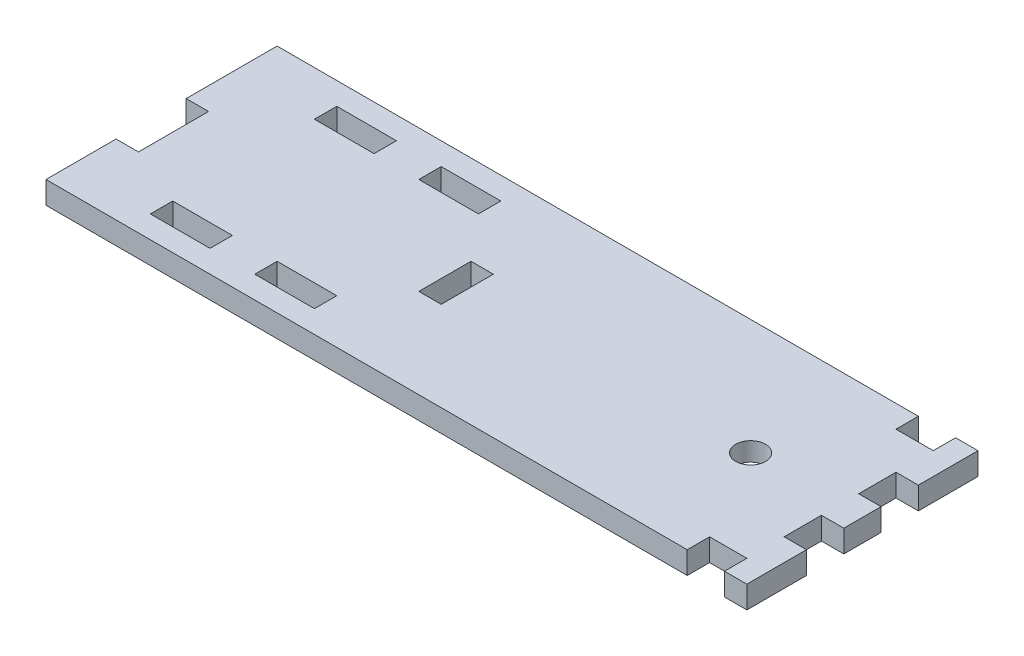
SolidWorks part; units mm, degrees
ref_plane "Front Plane" through (0, 0, 0) normal (0, 0, 1) x (1, 0, 0)
ref_plane "Top Plane" through (0, 0, 0) normal (0, 1, 0) x (1, 0, 0)
ref_plane "Right Plane" through (0, 0, 0) normal (1, 0, 0) x (0, 0, -1)
sketch "Sketch1" plane through (0, 0, 0) normal (0, 1, 0) x (1, 0, 0)
  line L1 (-94, 31) -> (94, 31)
  line L2 (-94, 31) -> (-94, -31)
  line L3 (-94, -31) -> (94, -31)
  line L4 (94, 31) -> (94, -31)
  line L5 (-94, 31) -> (94, -31) construction
  line L6 (-94, -31) -> (94, 31) construction
  point P0 (0, 0)
  dimension "D2" = 62
  dimension "D1" = 188
sketch "Sketch2" plane through (0, 0, 0) normal (0, 0, 1) x (1, 0, 0)
  line L0 (0, 0) -> (0, 6) construction
  line L1 (-94, 0) -> (94, 0) construction
  dimension "D1" = 6
extrude "Boss-Extrude1" add sketch "Sketch1" along normal up to vertex (6 mm away) contours L2 L3 L4 L1 up to point (0, 6, 0)
sketch "Sketch3" plane through (0, 0, 0) normal (0, -1, 0) x (1, 0, 0)
  line L0 (64, 0) -> (94, 0)
  line L1 (94, -31) -> (94, 31) construction
  circle A0 centre (64, 0) radius 4
  dimension "D1" = 8
  dimension "D2" = 30
extrude "Cut-Extrude1" cut sketch "Sketch3" against normal through all contours A0 region at (60.1131, 0, 0)
sketch "Sketch5" plane through (0, 6, 0) normal (0, 1, 0) x (1, 0, 0)
  line L0 (94, 31) -> (94, -31) construction
  line L1 (94, -31) -> (88, -31)
  line L2 (94, -31) -> (94, -25)
  line L3 (94, -25) -> (88, -25)
  line L4 (88, -31) -> (88, -25)
  line L5 (88, -25) -> (94, -25)
  line L6 (88, -25) -> (88, -15)
  line L7 (88, -15) -> (94, -15)
  line L8 (94, -25) -> (94, -15)
  line L9 (-94, 31) -> (94, 31) construction
  line L10 (94, -15) -> (88, -15)
  line L11 (94, -15) -> (94, -5)
  line L12 (94, -5) -> (88, -5)
  line L13 (88, -15) -> (88, -5)
  line L14 (88, -5) -> (94, -5)
  line L15 (88, -5) -> (88, 5)
  line L16 (88, 5) -> (94, 5)
  line L17 (94, -5) -> (94, 5)
  line L18 (94, 5) -> (88, 5)
  line L19 (94, 5) -> (94, 15)
  line L20 (94, 15) -> (88, 15)
  line L21 (88, 5) -> (88, 15)
  line L22 (88, 15) -> (94, 15)
  line L23 (88, 15) -> (88, 25)
  line L24 (88, 25) -> (94, 25)
  line L25 (94, 15) -> (94, 25)
  line L26 (94, 25) -> (88, 25)
  line L27 (94, 25) -> (94, 31)
  line L28 (94, 31) -> (88, 31)
  line L29 (88, 25) -> (88, 31)
  line M33 (94, -31) -> (94, 31)
  dimension "D1" = 6
  dimension "D2" = 6
  dimension "D3" = 10
extrude "Cut-Extrude2" cut sketch "Sketch5" against normal through all contours L13 L7 L12 M33 | L21 L16 L20 M33 region at (91, 6, 10) region at (91, 6, -10)
sketch "Sketch6" plane through (0, 0, 0) normal (0, -1, 0) x (1, 0, 0)
  line L0 (88, 31) -> (88, 25) construction
  line L1 (78, 25) -> (88, 25)
  line L2 (78, 25) -> (78, 31)
  line L3 (78, 31) -> (88, 31)
  line L4 (88, 25) -> (88, 31)
  line L5 (-94, 31) -> (94, 31) construction
  line L7 (-18, -7) -> (-12, -7)
  line L8 (-18, -7) -> (-18, 7)
  line L9 (-18, 7) -> (-12, 7)
  line L10 (-12, -7) -> (-12, 7)
  line L11 (-28, 19) -> (-44, 19)
  line L12 (-28, 19) -> (-28, 25)
  line L13 (-28, 25) -> (-44, 25)
  line L14 (-44, 19) -> (-44, 25)
  line L15 (-72, 19) -> (-56, 19)
  line L16 (-72, 19) -> (-72, 25)
  line L17 (-72, 25) -> (-56, 25)
  line L18 (-56, 19) -> (-56, 25)
extrude "Cut-Extrude3" cut sketch "Sketch6" against normal through all
mirror "Mirror1" about plane through (0, 0, 0) normal (0, 0, 1) of "Cut-Extrude3"
sketch "Sketch7" plane through (0, 0, 0) normal (0, -1, 0) x (-1, 0, 0)
  line L0 (-68, 0) -> (-72, 0) construction
  line L1 (-68, -5) -> (-68, 5) construction
  line L2 (-45, -27) -> (-45, -31) construction
  line L3 (94, -31) -> (-78, -31) construction
  line L4 (-26, 0) -> (-64, 0) construction
  line L5 (-45, -19) -> (-45, 19) construction
  line L6 (-26, 5) -> (-26, -5) construction
  line L7 (-24, 5) -> (-24, -5)
  line L8 (-28, 5) -> (-28, -5)
  line L9 (-45, 13.8035) -> (-45, 24.1965) construction
  line L10 (-50.1965, 19) -> (-39.8035, 19) construction
  circle A0 centre (-45, 0) radius 27
  circle A1 centre (-64, 0) radius 4 construction
  circle A2 centre (-64, 0) radius 4
  circle A3 centre (-45, 0) radius 1
  arc A4 (-24, 5) -> (-28, 5) centre (-26, 5) ccw
  arc A5 (-28, -5) -> (-24, -5) centre (-26, -5) ccw
  circle A6 centre (-45, 24.1965) radius 1.25
  circle A7 centre (-39.8035, 19) radius 1.25
  circle A8 centre (-45, 13.8035) radius 1.25
  circle A9 centre (-50.1965, 19) radius 1.25
  point P17 (-45, 0)
  point P19 (-45, 0)
  point P21 (-26, 0)
  point P29 (-45, 19)
  point P32 (-45, 19)
  circle M17 centre (-64, 0) radius 4
  dimension "D3" = 2
  dimension "D6" = 2.5
  dimension "D1" = 4
  dimension "D2" = 4
  dimension "D4" = 4
  dimension "D5" = 10
extrude "Cut-Extrude4" cut sketch "Sketch7" against normal blind 1 contours A0 A9 A8 A7 A6 A5 L8 A4 L7 A3 M17 region at (71.2363, 0, 0)
sketch "Sketch9" plane through (0, 0, 0) normal (0, -1, 0) x (1, 0, 0)
  line L0 (-94, -31) -> (-94, 31) construction
  line L1 (-88, -6.6) -> (-94, -6.6)
  line L2 (-88, -6.6) -> (-88, 12.2)
  line L3 (-88, 12.2) -> (-94, 12.2)
  line L4 (-94, -6.6) -> (-94, 12.2)
  line L5 (-94, 12.2) -> (-88, 12.2) construction
  line M45 (-94, 31) -> (-94, -31)
extrude "Cut-Extrude5" cut sketch "Sketch9" against normal through all contours L2 L3 L1 M45 region at (-91, 0, 2.8)
equation "\"glass_width\"= 150"
equation "\"glass_height\"= 100"
equation "\"glass_thickness\"= 4"
equation "\"brood_space\"= 42"
equation "\"t1\"= 6"
equation "\"t2\"= 6"
equation "\"box_depth\"= \"brood_space\" + \"glass_thickness\" + \"glass_thickness\" + \"t2\" + \"t2\""
equation "\"box_width\"= \"glass_width\" + \"t1\" + \"t1\""
equation "\"food_height\"= 70"
equation "\"box_height\"= \"glass_height\" + ( \"t1\" * 3 ) + \"food_height\""
equation "\"D1@Sketch2\"= \"t1\""
equation "\"entry_height\"= 24"
equation "\"entry_diameter\"= 8"
equation "\"food_top_clearance\"= 10"
equation "\"bar_width\"= 20"
equation "\"glassblocker_lower_height\"= 10"
equation "\"D2@Sketch1\"=\"box_depth\""
equation "\"D1@Sketch1\"=\"box_height\""
equation "\"D1@Sketch3\"=\"entry_diameter\""
equation "\"D2@Sketch3\"=\"entry_height\" + \"t1\""
equation "\"D1@Sketch5\"=\"t1\""
equation "\"D2@Sketch5\"=\"t2\""
